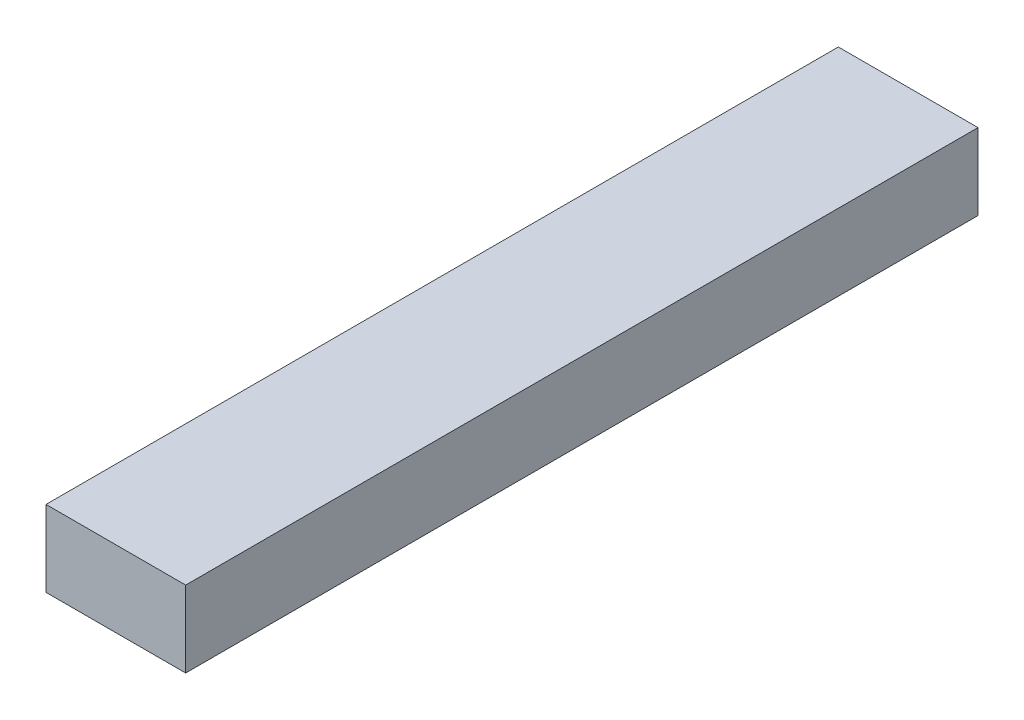
SolidWorks part; units mm, degrees
material "Простая углеродистая сталь"
ref_plane "Спереди" through (0, 0, 0) normal (0, 0, 1) x (1, 0, 0)
ref_plane "Сверху" through (0, 0, 0) normal (0, 1, 0) x (1, 0, 0)
ref_plane "Справа" through (0, 0, 0) normal (1, 0, 0) x (0, 0, -1)
sketch "Эскиз1" plane through (0, 0, 0) normal (0, 1, 0) x (1, 0, 0)
  line L1 (0, 0) -> (55, 0)
  line L2 (0, 0) -> (0, 312)
  line L3 (0, 312) -> (55, 312)
  line L4 (55, 0) -> (55, 312)
extrude "Бобышка-Вытянуть1" add sketch "Эскиз1" along normal blind 30
